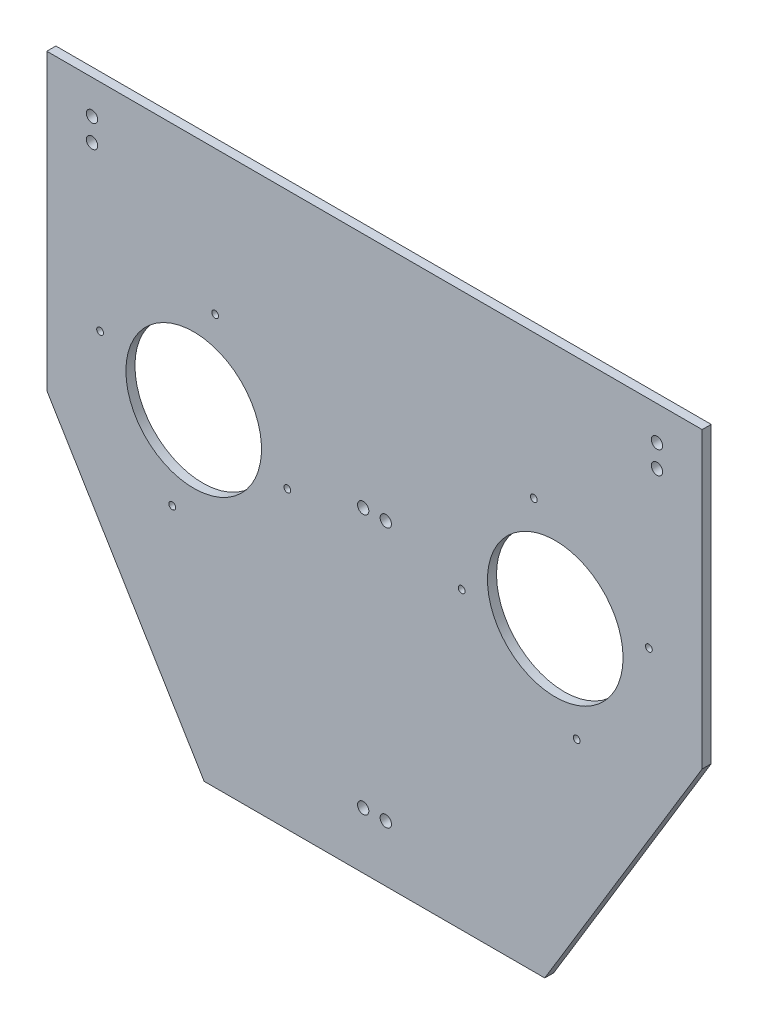
SolidWorks part; units mm, degrees
ref_plane "Front Plane" through (0, 0, 0) normal (0, 0, 1) x (1, 0, 0)
ref_plane "Top Plane" through (0, 0, 0) normal (0, 1, 0) x (1, 0, 0)
ref_plane "Right Plane" through (0, 0, 0) normal (1, 0, 0) x (0, 0, -1)
sketch "Sketch1" plane through (0, 0, 0) normal (0, 0, 1) x (1, 0, 0)
  line L0 (-125, 100) -> (125, 100) construction
  line L1 (-125, 0) -> (125, 0) construction
  line L2 (-145, -10.0794) -> (-75.355, -125)
  line L3 (-75.355, -125) -> (75.355, -125)
  line L4 (75.355, -125) -> (145, -10.0794)
  line L5 (-125, 105) -> (-125, 95) construction
  line L6 (0, -125) -> (0, 100) construction
  line L7 (-145, 120) -> (145, 120)
  line L8 (145, 120) -> (145, -10.0794)
  line L11 (-145, -10.0794) -> (-145, 120)
  line L12 (125, 105) -> (125, 95) construction
  line L13 (-5, -100) -> (5, -100) construction
  circle A0 centre (-125, 100) radius 12.5 construction
  circle A10 centre (-125, 0) radius 12.5 construction
  circle A11 centre (125, 0) radius 12.5 construction
  circle A12 centre (-125, 0) radius 17.5 construction
  circle A13 centre (-125, 100) radius 17.5 construction
  circle A25 centre (-125, 95) radius 2.5
  circle A26 centre (-125, 105) radius 2.5
  circle A27 centre (125, 95) radius 2.5
  circle A28 centre (125, 105) radius 2.5
  circle A29 centre (5, -100) radius 2.5
  circle A30 centre (-5, -100) radius 2.5
  point P12 (0, 100)
  point P15 (0, -100)
  point P45 (0, 120)
  dimension "D1" = 25
  dimension "D2" = 5
  dimension "D4" = 100
  dimension "D6" = 5
  dimension "D11" = 20
  dimension "D12" = 20
  dimension "D7" = 10
  dimension "D8" = 250
  dimension "D3" = 25
  dimension "D5" = 100
extrude "Boss-Extrude1" add sketch "Sketch1" along normal blind 4
sketch "Sketch2" plane through (0, 0, 4) normal (0, 0, 1) x (1, 0, 0)
  line L0 (121.4264, 24.4924) -> (38.5736, 5.5076) construction
  line L1 (89.4924, -26.4264) -> (70.5076, 56.4264) construction
  line L2 (0, 0) -> (0, 96.4486) construction
  line L3 (145, 120) -> (-145, 120) construction
  line L4 (-145, 120) -> (-145, -10.0794) construction
  line L5 (-80, 15) -> (80, 15) construction
  line L6 (-5, 15) -> (5, 15) construction
  circle A0 centre (80, 15) radius 42.5 construction
  circle A1 centre (38.5736, 5.5076) radius 1.5
  circle A2 centre (70.5076, 56.4264) radius 1.5
  circle A3 centre (121.4264, 24.4924) radius 1.5
  circle A4 centre (89.4924, -26.4264) radius 1.5
  circle A5 centre (80, 15) radius 30
  circle A6 centre (-38.5736, 5.5076) radius 1.5
  circle A7 centre (-70.5076, 56.4264) radius 1.5
  circle A8 centre (-89.4924, -26.4264) radius 1.5
  circle A9 centre (-121.4264, 24.4924) radius 1.5
  circle A10 centre (-80, 15) radius 42.5 construction
  circle A11 centre (-80, 15) radius 30
  circle A12 centre (-80, 15) radius 47.5 construction
  circle A15 centre (-5, 15) radius 2.5
  circle A16 centre (5, 15) radius 2.5
  point P6 (80, 15)
  point P27 (-80, 15)
  point P30 (0, 15)
  dimension "D1" = 85
  dimension "D2" = 3
  dimension "D3" = 60
  dimension "D4" = 95
  dimension "D5" = 5
  dimension "D6" = 105
  dimension "D7" = 65
  dimension "D8" = 10
extrude "Cut-Extrude1" cut sketch "Sketch2" against normal blind 10
equation "\"D1@Sketch1\" = \"cf_tube_outer_diameter\""
equation "\"mid_plate_mid_to_top\" = 100mm"
equation "\"mid_plate_mid_to_bottom\" = 100mm"
equation "\"mid_plate_horizontal_spacing\" = 250mm"
equation "\"cf_tube_outer_diameter\" = 25mm"
equation "\"D4@Sketch1\"=\"mid_plate_mid_to_top\""
equation "\"cf_tube_inner_diameter\" = 21mm"
equation "\"mid_tube_length\" = 500mm"
equation "\"cf_plate_thickness\" = 4mm"
equation "\"D1@Boss-Extrude1\"=\"cf_plate_thickness\""
equation "\"D8@Sketch1\"=\"mid_plate_horizontal_spacing\""
equation "\"D5@Sketch1\"=\"mid_plate_mid_to_bottom\""
